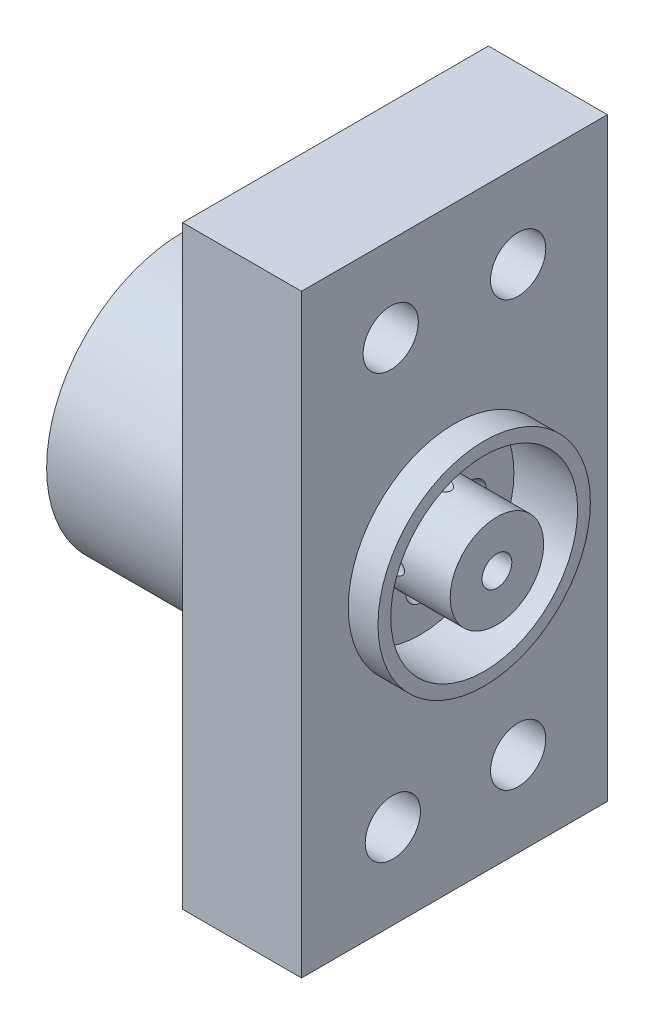
SolidWorks part; units mm, degrees
ref_plane "plan de symétrie" through (0, 0, 0) normal (0, 0, 1) x (1, 0, 0)
ref_plane "Dessus" through (0, 0, 0) normal (0, 1, 0) x (1, 0, 0)
ref_plane "plan d'appui" through (0, 0, 0) normal (1, 0, 0) x (0, 0, -1)
sketch "Esquisse1" plane through (0, 0, 0) normal (1, 0, 0) x (0, 0, -1)
  line L1 (18, -35) -> (-18, -35)
  line L2 (18, -35) -> (18, 35)
  line L3 (18, 35) -> (-18, 35)
  line L4 (-18, -35) -> (-18, 35)
extrude "Base-Extrusion" add sketch "Esquisse1" against normal blind 14
sketch "Esquisse10" plane through (-14, 0, 0) normal (-1, 0, 0) x (0, 0, 1)
  line L0 (-18, -35) -> (-18, 35) construction
  line L1 (18, -35) -> (-18, -35) construction
  circle A0 centre (0, 0) radius 16
  point P6 (0, 0)
  dimension "D1" = 32
  dimension "D2" = 18
  dimension "D3" = 35
extrude "Boss.-Extru.3" add sketch "Esquisse10" along normal blind 18
sketch "Esquisse3" plane through (0, 0, 0) normal (1, 0, 0) x (0, 0, -1)
  circle A0 centre (0, 0) radius 12.5
  circle A1 centre (0, 0) radius 12.5 construction
extrude "Boss.-Extru.2" add sketch "Esquisse3" along normal blind 5
chamfer "Chanfrein1" distance 0.5 angle 45 1 edges at (5, 0, -12.5)
hole_wizard "Chambrage pour vis à tête cylindrique à 6 pans creux (vis CHC) M51" positions "Esquisse5" profile "Esquisse4" counterbore size "M5" standard "ISO" end condition through all
sketch "Esquisse5" plane through (-14, 0, 0) normal (-1, 0, 0) x (0, 0, 1)
  line L0 (0, 0) -> (0, 40) construction
  line L1 (7.5, 25) -> (7.5, -37.9674) construction
  line L2 (-7.5, 25) -> (-7.5, -40.4301) construction
  line L3 (-7.5, -25) -> (7.2521, -25) construction
  point P0 (-7.5, 25)
  point P3 (7.5, 25)
  point P4 (7.2521, -25)
  point P6 (-7.5, -25)
  dimension "D1" = 7.5
  dimension "D2" = 25
  dimension "D3" = 25
sketch "Esquisse4" plane through (-14, 25, -7.5) normal (0, 1, 0) x (0, 0, 1)
  line L0 (0, 0) -> (0, 19)
  line L1 (0, 19) -> (3.25, 19)
  line L3 (3.25, 19) -> (3.25, 7)
  line L4 (3.25, 7) -> (6, 7)
  line L5 (6, 7) -> (6, 0)
  line L7 (6, 0) -> (0, 0)
  line L11 (0, -6.35) -> (0, 107.95) construction
  dimension "Diamètre du perçage jusqu'au prochain" = 6.5
  dimension "Profondeur du perçage jusqu'au prochain" = 19
  dimension "Diamètre du chambrage" = 12
  dimension "Profondeur du chambrage" = 7
sketch "Esquisse6" plane through (0, 0, 0) normal (0, 0, 1) x (1, 0, 0)
  line L0 (0, 0) -> (14.8357, 0) construction
  line L3 (-32, 1.75) -> (5, 1.75)
  line L4 (5, -12.5) -> (5, 12.5) construction
  line L5 (5, 1.75) -> (5, 5.5)
  line L6 (5, 5.5) -> (-4, 5.5)
  line L7 (-4, 5.5) -> (-4, 11)
  line L9 (3.5, 13.8522) -> (3.5, 11)
  line L12 (8, 13.8522) -> (8, 0)
  line L13 (-32, 1.75) -> (-32, 0)
  line L15 (-32, 0) -> (8, 0)
  line L18 (0, 35) -> (0, -35) construction
  line L19 (-4, 11) -> (3.5, 11)
  line L20 (3.5, 13.8522) -> (8, 13.8522)
  dimension "D1" = 1.75
  dimension "D2" = 5.5
  dimension "D3" = 9
  dimension "D5" = 3.5
  dimension "D6" = 11
revolve "Enlèvement de matière-Révolution1" cut sketch "Esquisse6" angle 360 about L0
sketch "Esquisse7" plane through (-32, 4.864, 53.861) normal (-1, 0, 0) x (0, 0, 1)
  circle A1 centre (-53.861, -4.864) radius 1.75 construction
  point P0 (-53.861, -4.864)
sketch "Esquisse8" plane through (-32, 0, 0) normal (0, 1, 0) x (0, 0, 1)
  line L0 (0, 0) -> (0, 26.2962)
  line L1 (7.15, 22) -> (0, 26.2962)
  line L2 (-7.15, 22) -> (0, 26.2962) construction
  line L3 (7.15, 22) -> (7.15, 20)
  line L4 (7.15, 20) -> (7.2787, 20)
  line L5 (7.2787, 20) -> (7.903, 0)
  line L6 (-7.2787, 20) -> (-7.903, 0) construction
  line L7 (7.903, 0) -> (0, 0)
  line L8 (0, -6.35) -> (0, 107.95) construction
  line L11 (-7.15, 20) -> (-7.2787, 20) construction
  dimension "Diamètre du trou pour taraudage" = 14.3
  dimension "Profondeur du trou pour taraudage" = 22
  dimension "Diamètre du filetage" = 15.806
  dimension "Angle de filetage" = 3.576
  dimension "Profondeur du filetage" = 20
  dimension "Angle de pointe" = 118
hole_wizard "Perçage1" positions "Esquisse7" profile "Esquisse8" size "3/8" standard "ISO"
cosmetic thread "Représentation de filetage1" parameters "D1"=17
sketch "Esquisse9" plane through (0, 0, 0) normal (0, 0, 1) x (1, 0, 0)
  line L0 (0, 0) -> (-18.0493, 0) construction
  line L1 (3.5, 0) -> (0, 0) construction
  line L2 (-35.7968, -7.7001) -> (3.5, 9.0466) construction
  line L3 (-11.9072, 4.383) -> (0.4372, 9.6437)
  line L4 (3.5, -12.5) -> (3.5, 12.5) construction
  line L7 (1.1233, 8.0338) -> (-11.2211, 2.7731)
  line L8 (-11.2211, 2.7731) -> (-11.9072, 4.383)
  line L9 (1.1233, 8.0338) -> (0.4372, 9.6437)
  circle A0 centre (-32, -6.0821) radius 1.75 construction
  circle A1 centre (3.5, 9.0466) radius 1.75 construction
  dimension "D2" = 1.75
revolve "Enlèvement de matière-Révolution2" cut sketch "Esquisse9" angle 360 about L2
ref_axis "Axe1" through (50, 0, 0) along (-1, 0, 0)
pattern_circular "Répétition circulaire1" count 4 every 90 about axis through (50, 0, 0) along (-1, 0, 0) of "Enlèvement de matière-Révolution2"
